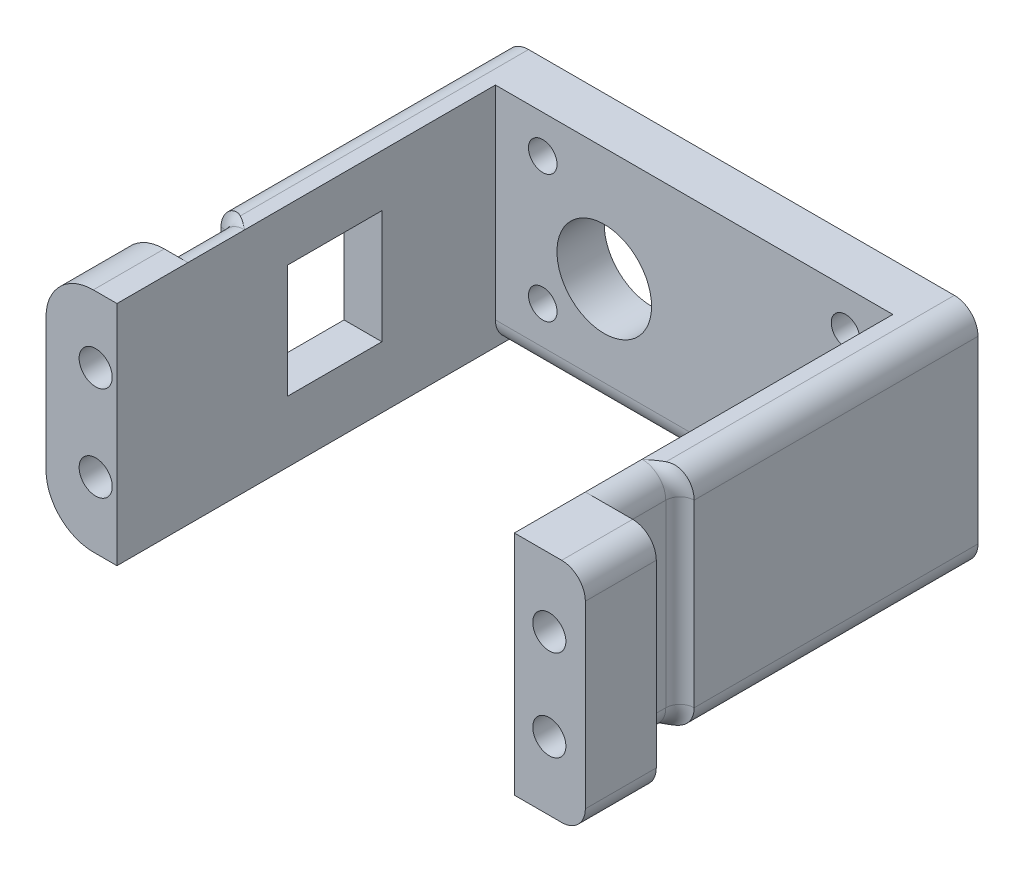
SolidWorks part; units mm, degrees
ref_plane "Front Plane" through (0, 0, 0) normal (0, 0, 1) x (1, 0, 0)
ref_plane "Top Plane" through (0, 0, 0) normal (0, 1, 0) x (1, 0, 0)
ref_plane "Right Plane" through (0, 0, 0) normal (1, 0, 0) x (0, 0, -1)
sketch "Sketch1" plane through (0, 0, 0) normal (0, 0, 1) x (1, 0, 0)
  line L1 (0, 0) -> (47, 0)
  line L2 (0, 0) -> (0, 24)
  line L3 (0, 24) -> (47, 24)
  line L4 (47, 0) -> (47, 24)
  dimension "D1" = 47
  dimension "D2" = 24
extrude "Boss-Extrude1" add sketch "Sketch1" along normal blind 5
sketch "Sketch2" plane through (0, 0, 5) normal (0, 0, 1) x (1, 0, 0)
  line L1 (0, 0) -> (47, 0) construction
  line L2 (0, 24) -> (0, 0) construction
  circle A0 centre (14, 12) radius 5
  dimension "D1" = 10
  dimension "D2" = 12
  dimension "D3" = 14
extrude "Cut-Extrude1" cut sketch "Sketch2" against normal through all
sketch "Sketch6" plane through (0, 0, 5) normal (0, 0, 1) x (1, 0, 0)
  line L0 (0, 0) -> (47, 0) construction
  line L1 (47, 24) -> (44.5, 24)
  line L2 (47, 24) -> (47, 0)
  line L3 (47, 0) -> (44.5, 0)
  line L4 (44.5, 24) -> (44.5, 0)
  line L5 (23.5, 24) -> (23.5, 0) construction
  line L6 (47, 24) -> (0, 24) construction
  line L7 (2.5, 24) -> (2.5, 0)
  line L8 (0, 0) -> (2.5, 0)
  line L9 (0, 24) -> (0, 0)
  line L10 (0, 24) -> (2.5, 24)
  dimension "D1" = 2.5
extrude "Boss-Extrude2" add sketch "Sketch6" along normal blind 40
sketch "Sketch7" plane through (47, 0, 0) normal (1, 0, 0) x (0, 0, -1)
  line L1 (-45, 24) -> (-37.5, 24)
  line L2 (-45, 24) -> (-45, 0)
  line L3 (-45, 0) -> (-37.5, 0)
  line L4 (-37.5, 24) -> (-37.5, 0)
extrude "Boss-Extrude3" add sketch "Sketch7" along normal blind 5
sketch "Sketch8" plane through (0, 0, 0) normal (-1, 0, 0) x (0, 0, 1)
  line L0 (45, 24) -> (0, 24) construction
  line L1 (45, 0) -> (37.5, 0)
  line L2 (45, 0) -> (45, 24)
  line L3 (45, 24) -> (37.5, 24)
  line L4 (37.5, 0) -> (37.5, 24)
  dimension "D1" = 7.5
extrude "Boss-Extrude4" add sketch "Sketch8" along normal blind 5
fillet "Fillet1" radius 2.5 1 edges at (0, 0, 18.75)
fillet "Fillet2" radius 2.5 rebuild error yes
fillet "Fillet3" radius 5 2 edges at (-5, 24, 41.25) (-5, 0, 41.25)
fillet "Fillet4" radius 2.5 1 edges at (0, 24, 18.75)
fillet "Fillet5" radius 2.5 2 edges at (47, 24, 18.75) (47, 0, 18.75)
fillet "Fillet6" radius 2.5 1 edges at (23.5, 0, 5)
fillet "Fillet7" radius 2.5 2 edges at (52, 24, 41.25) (52, 0, 41.25)
sketch "Sketch9" plane through (0, 0, 0) normal (-1, 0, 0) x (0, 0, 1)
  line L0 (0, 21.5) -> (0, 2.5) construction
  line L1 (27, 18.5) -> (15, 18.5)
  line L2 (27, 18.5) -> (27, 6.5)
  line L3 (27, 6.5) -> (15, 6.5)
  line L4 (15, 18.5) -> (15, 6.5)
  line L5 (37.5, 21.5) -> (0, 21.5) construction
  dimension "D1" = 12
  dimension "D2" = 12
  dimension "D3" = 15
  dimension "D4" = 3
extrude "Cut-Extrude2" cut sketch "Sketch9" against normal blind 5 and the other way blind 30
sketch "Sketch10" plane through (0, 0, 5) normal (0, 0, 1) x (1, 0, 0)
  line L1 (44.5, 24) -> (44.5, 2.5) construction
  line L2 (2.5, 2.5) -> (44.5, 2.5) construction
  line L3 (44.5, 13.25) -> (36.0272, 13.25) construction
  line L4 (23.5, 24) -> (23.5, 2.5) construction
  line L5 (44.5, 24) -> (2.5, 24) construction
  line L6 (2.5, 13.25) -> (10.9728, 13.25) construction
  circle A0 centre (39.5, 6.5) radius 1.51
  circle A1 centre (39.5, 20) radius 1.51
  circle A2 centre (39.5, 6.5) radius 1.51
  circle A3 centre (39.5, 20) radius 1.51
  circle A4 centre (7.5, 20) radius 1.51
  circle A5 centre (7.5, 6.5) radius 1.51
  circle A6 centre (7.5, 20) radius 1.51
  circle A7 centre (7.5, 6.5) radius 1.51
  dimension "D2" = 3.02
  dimension "D1" = 5
  dimension "D3" = 4
extrude "Cut-Extrude3" cut sketch "Sketch10" against normal through all contours A4 | A1 | A0 | A5 region at (7.5, 20, 5)
sketch "Sketch11" plane through (0, 0, 45) normal (0, 0, 1) x (1, 0, 0)
  line L0 (44.5, 12) -> (52.5193, 12) construction
  line L1 (44.5, 24) -> (44.5, 0) construction
  circle A0 centre (48.195, 16.797) radius 1.75
  circle A1 centre (48.195, 7.203) radius 1.75
  dimension "D1" = 3.5
extrude "Cut-Extrude4" cut sketch "Sketch11" against normal blind 12
sketch "Sketch12" plane through (0, 0, 45) normal (0, 0, 1) x (1, 0, 0)
  circle A0 centre (0.25, 7) radius 1.75
  circle A1 centre (0.25, 17) radius 1.75
  dimension "D1" = 3.5
  dimension "D2" = 3.5
extrude "Cut-Extrude5" cut sketch "Sketch12" against normal blind 12
sketch "Sketch13" plane through (0, 0, 0) normal (0, 0, -1) x (-1, 0, 0)
  line L0 (-2.5, 0) -> (-44.5, 0) construction
  line L1 (-2.5, 24) -> (-1, 24)
  line L2 (-2.5, 24) -> (-2.5, 0)
  line L3 (-2.5, 0) -> (-1, 0)
  line L4 (1.5, 21.5) -> (1.5, 2.5)
  line L5 (-23.5, 24) -> (-23.5, 14.6582) construction
  line L6 (-44.5, 24) -> (-2.5, 24) construction
  line L7 (-48.5, 21.5) -> (-48.5, 2.5)
  line L8 (-44.5, 0) -> (-46, 0)
  line L9 (-44.5, 24) -> (-44.5, 0)
  line L10 (-44.5, 24) -> (-46, 24)
  arc A0 (-1, 0) -> (1.5, 2.5) centre (-1, 2.5) ccw
  arc A1 (1.5, 21.5) -> (-1, 24) centre (-1, 21.5) ccw
  arc A2 (-48.5, 21.5) -> (-46, 24) centre (-46, 21.5) cw
  arc A3 (-46, 0) -> (-48.5, 2.5) centre (-46, 2.5) cw
  dimension "D2" = 2.5
  dimension "D1" = 4
extrude "Boss-Extrude5" add sketch "Sketch13" against normal blind 30
fillet "Fillet8" radius 1.5 3 edges at (0.7322, 0.7322, 30) (0.7322, 23.2678, 30) (0, 12, 30)
fillet "Fillet9" radius 1.5 3 edges at (46.2678, 0.7322, 30) (46.2678, 23.2678, 30) (47, 12, 30)
sketch "Sketch14" plane through (-1.5, 0, 0) normal (-1, 0, 0) x (0, 0, 1)
  line L0 (30, 2.5) -> (30, 21.5) construction
  line L1 (27, 18.5) -> (17, 18.5)
  line L2 (27, 18.5) -> (27, 6.5)
  line L3 (27, 6.5) -> (17, 6.5)
  line L4 (17, 18.5) -> (17, 6.5)
  line L5 (30, 2.5) -> (0, 2.5) construction
  dimension "D1" = 12
  dimension "D2" = 10
  dimension "D3" = 3
  dimension "D4" = 4
extrude "Cut-Extrude6" cut sketch "Sketch14" against normal blind 10
